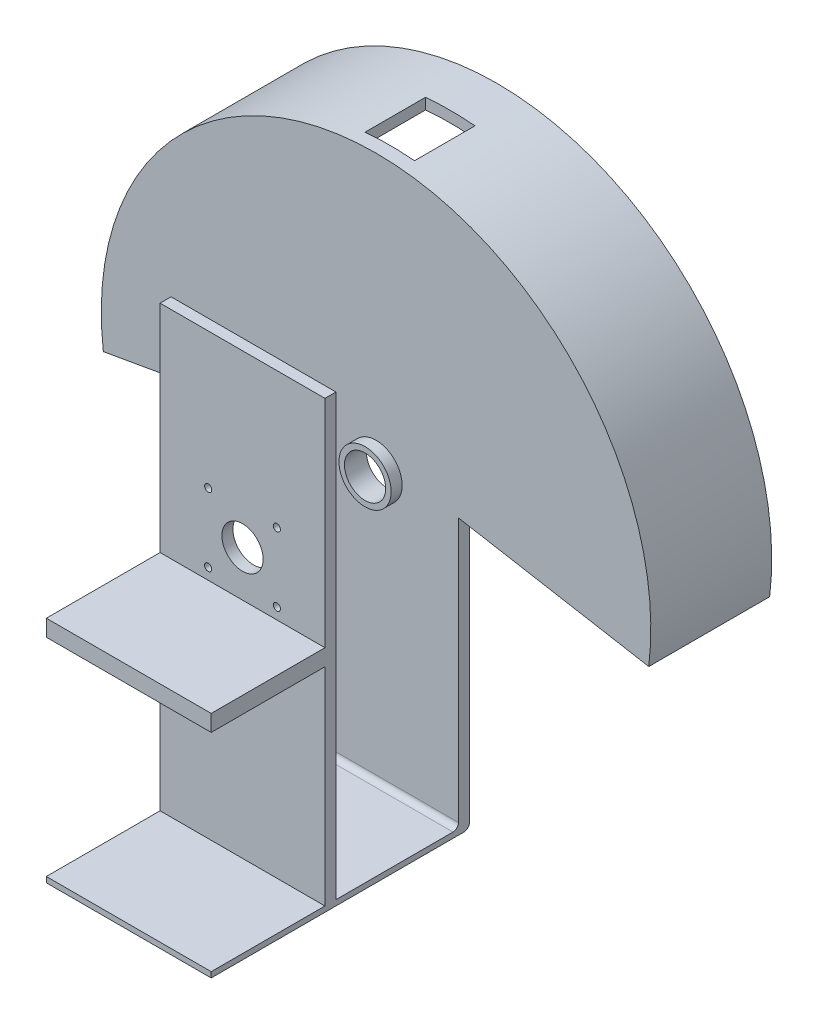
SolidWorks part; units mm, degrees
ref_plane "Front Plane" through (0, 0, 0) normal (0, 0, 1) x (1, 0, 0)
ref_plane "Top Plane" through (0, 0, 0) normal (0, 1, 0) x (1, 0, 0)
ref_plane "Right Plane" through (0, 0, 0) normal (1, 0, 0) x (0, 0, -1)
sketch "Sketch1" plane through (0, 0, 0) normal (0, 0, 1) x (1, 0, 0)
  line L0 (-38.1, 0) -> (-38.1, -127)
  line L1 (38.1, 0) -> (38.1, -127)
  line L2 (-38.1, 0) -> (-126.0496, -15.5079)
  line L3 (38.1, 0) -> (126.0496, -15.5079)
  line L4 (0, 0) -> (-38.1, 0) construction
  line L5 (0, 0) -> (38.1, 0) construction
  line L6 (-38.1, -127) -> (38.1, -127)
  arc A1 (-126.0496, -15.5079) -> (126.0496, -15.5079) centre (0, 0) cw
  circle A2 centre (0, 0) radius 9.525
  dimension "D1" = 127
  dimension "D5" = 19.05
  dimension "D2" = 127
  dimension "D3" = 80
  dimension "D4" = 76.2
extrude "Boss-Extrude1" add sketch "Sketch1" along normal blind 5.08
sketch "Sketch2" plane through (0, 0, 0) normal (0, 0, -1) x (-1, 0, 0)
  line L0 (-38.1, 0) -> (-126.0496, -15.5079)
  line L1 (38.1, 0) -> (126.0496, -15.5079)
  line L6 (-121.0397, -14.6245) -> (-126.0496, -15.5079)
  line L7 (121.0397, -14.6245) -> (126.0496, -15.5079)
  line L8 (-126.0496, -15.5079) -> (-121.0397, -14.6245)
  line L9 (121.0397, -14.6245) -> (126.0496, -15.5079)
  line L10 (-126.0496, -15.5079) -> (-121.0397, -14.6245)
  line L11 (121.0397, -14.6245) -> (126.0496, -15.5079)
  arc A0 (-126.0496, -15.5079) -> (126.0496, -15.5079) centre (0, 0) cw
  arc A1 (-121.0397, -14.6245) -> (121.0397, -14.6245) centre (0, 0) cw
  arc A2 (126.0496, -15.5079) -> (-126.0496, -15.5079) centre (0, 0) ccw construction
  arc M10 (126.0496, -15.5079) -> (-126.0496, -15.5079) centre (0, 0) ccw
  line M11 (-126.0496, -15.5079) -> (-38.1, 0)
  dimension "D1" = 5.08
extrude "Boss-Extrude3" add sketch "Sketch2" along normal blind 50.8 contours A1 L1 M11 M10 region at (124.0504, -12.198, 0)
sketch "Sketch3" plane through (-38.1, 0, 0) normal (-1, 0, 0) x (0, 0, 1)
  line L1 (5.08, -127) -> (119.38, -127)
  line L2 (5.08, -127) -> (5.08, -124.46)
  line L3 (5.08, -124.46) -> (119.38, -124.46)
  line L4 (119.38, -127) -> (119.38, -124.46)
  dimension "D1" = 2.54
  dimension "D2" = 114.3
extrude "Boss-Extrude4" add sketch "Sketch3" against normal up to surface (76.2 mm away) up to face at (38.1, -63.5, 2.54)
fillet "Fillet1" radius 2.54 1 edges at (0, -127, 0)
fillet "Fillet2" radius 2.54 1 edges at (0, -124.46, 5.08)
sketch "Sketch4" plane through (0, 0, 5.08) normal (0, 0, 1) x (1, 0, 0)
  circle A0 centre (0, 0) radius 9.525
  circle A1 centre (0, 0) radius 12.065
  circle A2 centre (0, 0) radius 9.525 construction
  dimension "D1" = 2.54
extrude "Boss-Extrude5" add sketch "Sketch4" along normal blind 5.08
sketch "Sketch5" plane through (38.1, 0, 0) normal (1, 0, 0) x (0, 0, -1)
  line L0 (-7.62, -124.46) -> (-119.38, -124.46) construction
  line L1 (-61.722, -124.46) -> (-66.802, -124.46)
  line L2 (-61.722, -124.46) -> (-61.722, 78.74)
  line L3 (-61.722, 78.74) -> (-66.802, 78.74)
  line L4 (-66.802, -124.46) -> (-66.802, 78.74)
  line L5 (-5.08, -121.92) -> (-5.08, 0) construction
  dimension "D1" = 56.642
  dimension "D2" = 5.08
  dimension "D3" = 203.2
extrude "Boss-Extrude6" add sketch "Sketch5" against normal up to surface (76.2 mm away) up to face at (-38.1, -93.794, 32.2535)
sketch "Sketch6" plane through (0, 0, 61.722) normal (0, 0, -1) x (-1, 0, 0)
  circle A0 centre (0, 0) radius 9.525
extrude "Cut-Extrude1" cut sketch "Sketch6" against normal up to next
sketch "Sketch7" plane through (-38.1, 0, 0) normal (-1, 0, 0) x (0, 0, 1)
  line L0 (61.722, 78.74) -> (61.722, -124.46) construction
  line L1 (61.722, -21.082) -> (119.38, -21.082)
  line L2 (61.722, -21.082) -> (61.722, -28.702)
  line L3 (61.722, -28.702) -> (119.38, -28.702)
  line L4 (119.38, -21.082) -> (119.38, -28.702)
  line L5 (119.38, -127) -> (119.38, -124.46) construction
  line L6 (-50.8, 0) -> (66.802, 0) construction
  line L7 (-50.8, 127) -> (-50.8, -15.5079) construction
  line L8 (66.802, 78.74) -> (66.802, -124.46) construction
  dimension "D1" = 7.62
  dimension "D2" = 21.082
extrude "Boss-Extrude7" add sketch "Sketch7" against normal up to surface (76.2 mm away) up to face at (38.1, -70.1493, 42.923)
sketch "Sketch8" plane through (0, 0, 66.802) normal (0, 0, 1) x (1, 0, 0)
  line L0 (-15.875, 15.875) -> (15.875, 15.875) construction
  line L1 (15.875, 15.875) -> (15.875, -15.875) construction
  line L2 (15.875, -15.875) -> (-15.875, -15.875) construction
  line L3 (-15.875, -15.875) -> (-15.875, 15.875) construction
  line L4 (-15.875, 15.875) -> (15.875, -15.875) construction
  line L5 (15.875, 15.875) -> (-15.875, -15.875) construction
  circle A0 centre (-15.875, 15.875) radius 1.651
  circle A1 centre (15.875, 15.875) radius 1.651
  circle A2 centre (-15.875, -15.875) radius 1.651
  circle A3 centre (15.875, -15.875) radius 1.651
  point P8 (0, 0)
  dimension "D1" = 3.302
  dimension "D2" = 15.875
extrude "Cut-Extrude2" cut sketch "Sketch8" against normal blind 5.08
sketch "Sketch9" plane through (0, 0, 0) normal (0, 1, 0) x (1, 0, 0)
  line L0 (-127, -5.08) -> (127, -5.08) construction
  line L1 (-11.43, 29.21) -> (11.43, 29.21)
  line L2 (-11.43, 29.21) -> (-11.43, 1.27)
  line L3 (-11.43, 1.27) -> (11.43, 1.27)
  line L4 (11.43, 29.21) -> (11.43, 1.27)
  point P4 (0, 1.27)
  dimension "D1" = 22.86
  dimension "D2" = 27.94
  dimension "D3" = 6.35
extrude "Cut-Extrude3" cut sketch "Sketch9" along normal through all
